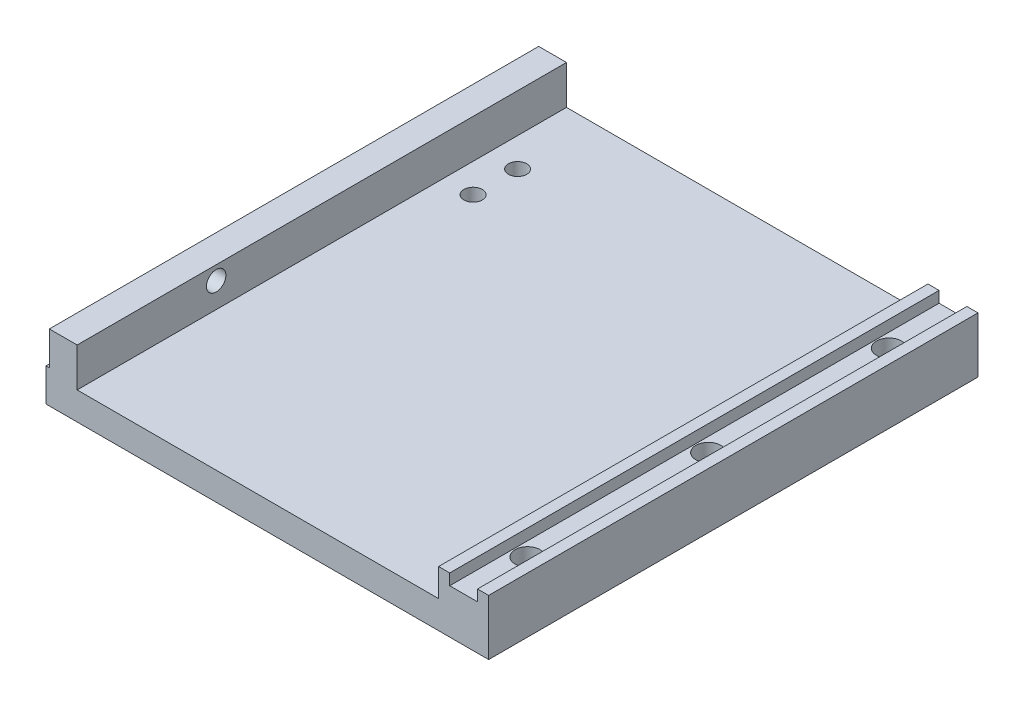
SolidWorks part; units mm, degrees
ref_plane "前视基准面" through (0, 0, 0) normal (0, 0, 1) x (1, 0, 0)
ref_plane "上视基准面" through (0, 0, 0) normal (0, 1, 0) x (1, 0, 0)
ref_plane "右视基准面" through (0, 0, 0) normal (1, 0, 0) x (0, 0, -1)
sketch "草图1" plane through (0, 0, 0) normal (0, 0, 1) x (1, 0, 0)
  line L0 (-9, 10) -> (-9, 5)
  line L1 (-9, 10) -> (-7, 10)
  line L2 (-7, 10) -> (-7, 8)
  line L3 (-7, 8) -> (-2, 8)
  line L4 (-2, 8) -> (-2, 10)
  line L5 (-2, 10) -> (0, 10)
  line L6 (0, 10) -> (0, 0)
  line L7 (-79.6, 0) -> (-79.6, 5.9)
  line L8 (-79.6, 5.9) -> (-79, 5.9)
  line L9 (-79, 5.9) -> (-79, 12)
  line L10 (-74, 12) -> (-79, 12)
  line L11 (-74, 12) -> (-74, 5)
  line L12 (-9, 5) -> (-74, 5)
  line L13 (0, 0) -> (-79.6, 0)
  line L21 (-0.5, 0) -> (-0.5, 4.4) construction
  line L22 (-8.5, 4.4) -> (-8.5, 0) construction
  line L24 (-6.75, 8) -> (-6.75, 4.4) construction
  line L30 (-74, 11.25) -> (-79, 11.25) construction
extrude "凸台-拉伸1" add sketch "草图1" along normal blind 88
hole_wizard "M4 六角凹头螺钉的柱形沉头孔1" positions "草图2" profile "草图3" counterbore size "M4" standard "ISO" end condition through all
sketch "草图2" plane through (0, 0, 0) normal (0, -1, 0) x (-1, 0, 0)
  line L0 (79.6, -44) -> (-18.4609, -44) construction
  line L1 (79.6, -88) -> (79.6, 0) construction
  line L3 (0, -88) -> (0, 0) construction
  point P0 (4.5, -11.5)
  point P2 (4.5, -44)
  point P4 (4.5, -76.5)
  dimension "D1" = 65
  dimension "D2" = 4.5
sketch "草图3" plane through (-4.5, 0, 11.5) normal (1, 0, 0) x (0, 0, -1)
  line L0 (0, 0) -> (0, 12)
  line L1 (0, 12) -> (2.25, 12)
  line L3 (2.25, 12) -> (2.25, 4.4)
  line L4 (2.25, 4.4) -> (4, 4.4)
  line L5 (4, 4.4) -> (4, 0)
  line L7 (4, 0) -> (0, 0)
  line L11 (0, -6.35) -> (0, 107.95) construction
  dimension "通孔孔直径" = 4.5
  dimension "通孔孔深度" = 12
  dimension "柱形沉头孔直径" = 8
  dimension "柱形沉头孔深度" = 4.4
hole_wizard "M4 螺纹孔1" positions "草图4" profile "草图5" tap size "M4" standard "ISO" end condition through all
sketch "草图4" plane through (0, 0, 0) normal (0, -1, 0) x (-1, 0, 0)
  line L0 (0, -88) -> (0, 0) construction
  line L1 (79.6, 0) -> (0, 0) construction
  point P0 (68.8, -14)
  point P2 (68.8, -22)
  dimension "D1" = 68.8
  dimension "D2" = 14
  dimension "D3" = 22
sketch "草图5" plane through (-68.8, 0, 14) normal (1, 0, 0) x (0, 0, -1)
  line L0 (0, 0) -> (0, 12)
  line L1 (0, 12) -> (1.65, 12)
  line L2 (1.65, 12) -> (1.65, 0)
  line L5 (1.65, 0) -> (0, 0)
  line L11 (0, -6.35) -> (0, 107.95) construction
  dimension "通孔螺纹孔钻头直径" = 3.3
  dimension "通孔螺纹孔钻头深度" = 12
cosmetic thread "孔螺蚊线1" parameters "D2"=4
cosmetic thread "孔螺蚊线2" parameters "D2"=4
hole_wizard "M3 螺纹孔1" positions "草图6" profile "草图7" tap size "M3" standard "ISO"
sketch "草图6" plane through (-79.6, 0, 0) normal (-1, 0, 0) x (0, 0, 1)
  line L0 (44, 5.9) -> (44, -5.3544) construction
  line L1 (88, 5.9) -> (0, 5.9) construction
  line L4 (88, 0) -> (0, 0) construction
  point P0 (11.5, 3)
  point P2 (44, 3)
  point P4 (76.5, 3)
  dimension "D1" = 65
  dimension "D2" = 3
cosmetic thread "孔螺蚊线3" parameters "D1"=8, "D2"=3
cosmetic thread "孔螺蚊线4" parameters "D1"=8, "D2"=3
cosmetic thread "孔螺蚊线5" parameters "D1"=8, "D2"=3
sketch "草图7" plane through (-79.6, 3, 11.5) normal (0, 1, 0) x (0, 0, 1)
  line L0 (0, 0) -> (0, 10.2511)
  line L1 (0, 10.2511) -> (1.25, 9.5)
  line L2 (1.25, 9.5) -> (1.25, 0)
  line L5 (1.25, 0) -> (0, 0)
  line L10 (0, 10.2511) -> (-1.25, 9.5) construction
  line L11 (0, -6.35) -> (0, 107.95) construction
  dimension "螺纹孔钻头直径" = 2.5
  dimension "螺纹孔钻头深度" = 9.5
  dimension "导头角度" = 118
sketch "草图8" plane through (-79, 0, 0) normal (-1, 0, 0) x (0, 0, 1)
  line L0 (88, 12) -> (0, 12) construction
  line L1 (0, 12) -> (0, 5.9) construction
  circle A0 centre (63, 9.5) radius 1.75
  dimension "D1" = 3.5
  dimension "D2" = 2.5
  dimension "D3" = 63
extrude "切除-拉伸1" cut sketch "草图8" against normal blind 5
sketch "草图9" plane through (0, 5.9, 0) normal (0, 1, 0) x (1, 0, 0)
  line L1 (-79.6, -88) -> (-79, -88)
  line L2 (-79.6, -88) -> (-79.6, 0)
  line L3 (-79.6, 0) -> (-79, 0)
  line L4 (-79, -88) -> (-79, 0)
extrude "凸台-拉伸2" add sketch "草图9" along normal blind 0.05
